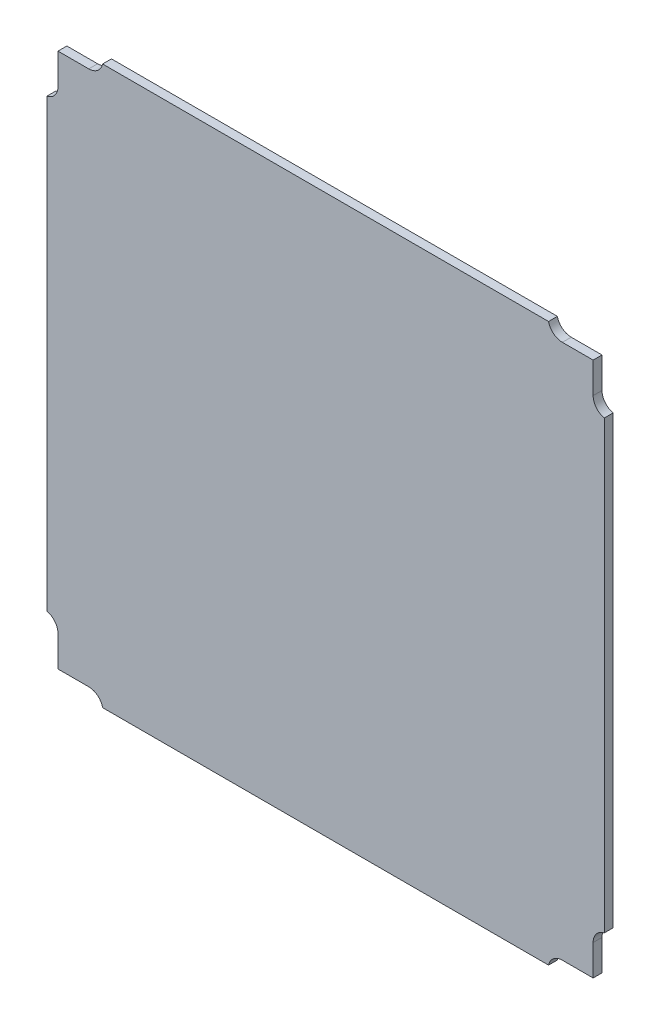
SolidWorks part; units mm, degrees
ref_plane "Front Plane" through (0, 0, 0) normal (0, 0, 1) x (1, 0, 0)
ref_plane "Top Plane" through (0, 0, 0) normal (0, 1, 0) x (1, 0, 0)
ref_plane "Right Plane" through (0, 0, 0) normal (1, 0, 0) x (0, 0, -1)
sketch "Sketch1" plane through (0, 0, 0) normal (0, 0, 1) x (1, 0, 0)
  line L0 (-40, 50) -> (-40, 48)
  line L1 (-50, -50) -> (50, -50)
  line L2 (-50, -50) -> (-50, 50)
  line L3 (-50, 50) -> (50, 50)
  line L4 (50, -50) -> (50, 50)
  line L5 (-50, -50) -> (50, 50) construction
  line L6 (-50, 50) -> (50, -50) construction
  line L7 (-50, 50) -> (-40, 50)
  line L8 (-50, 50) -> (-50, 40)
  line L9 (-40, 48) -> (-48, 48)
  line L10 (-48, 48) -> (-48, 40)
  line L11 (50, 50) -> (40, 50)
  line L12 (50, 50) -> (50, 40)
  line L13 (-48, 40) -> (-50, 40)
  line L14 (50, 40) -> (48, 40)
  line L15 (-50, -50) -> (-37.8649, -50)
  line L16 (-50, -50) -> (-50, -37.8649)
  line L17 (50, 50) -> (50, 40)
  line L18 (50, 50) -> (40, 50)
  line L19 (50, -50) -> (41.5, -50)
  line L20 (50, -50) -> (50, -41.5)
  line L21 (48, 40) -> (48, 48)
  line L22 (48, 48) -> (40, 48)
  line L23 (40, 48) -> (40, 50)
  line L24 (40, -50) -> (40, -48)
  line L25 (50, -50) -> (40, -50)
  line L26 (50, -50) -> (50, -40)
  line L27 (40, -48) -> (48, -48)
  line L28 (48, -48) -> (48, -40)
  line L29 (48, -40) -> (50, -40)
  line L30 (-50, -40) -> (-48, -40)
  line L31 (-50, -50) -> (-50, -40)
  line L32 (-50, -50) -> (-40, -50)
  line L33 (-48, -40) -> (-48, -48)
  line L34 (-48, -48) -> (-40, -48)
  line L35 (-40, -48) -> (-40, -50)
  point P0 (0, 0)
  point P38 (0, 0)
  dimension "D1" = 100
  dimension "D2" = 100
  dimension "D3" = 2
  dimension "D4" = 10
  dimension "D5" = 4
extrude "Boss-Extrude1" add sketch "Sketch1" along normal blind 1.5875 contours L1 L4 L3 L2 region at (0, 0, 0)
fillet "Fillet1" radius 2.54 8 edges at (-48, -40, 0.7937) (-40, -48, 0.7937) (40, -48, 0.7937) (48, -40, 0.7937) (48, 40, 0.7937) (40, 48, 0.7937) (-40, 48, 0.7937) (-48, 40, 0.7937)
